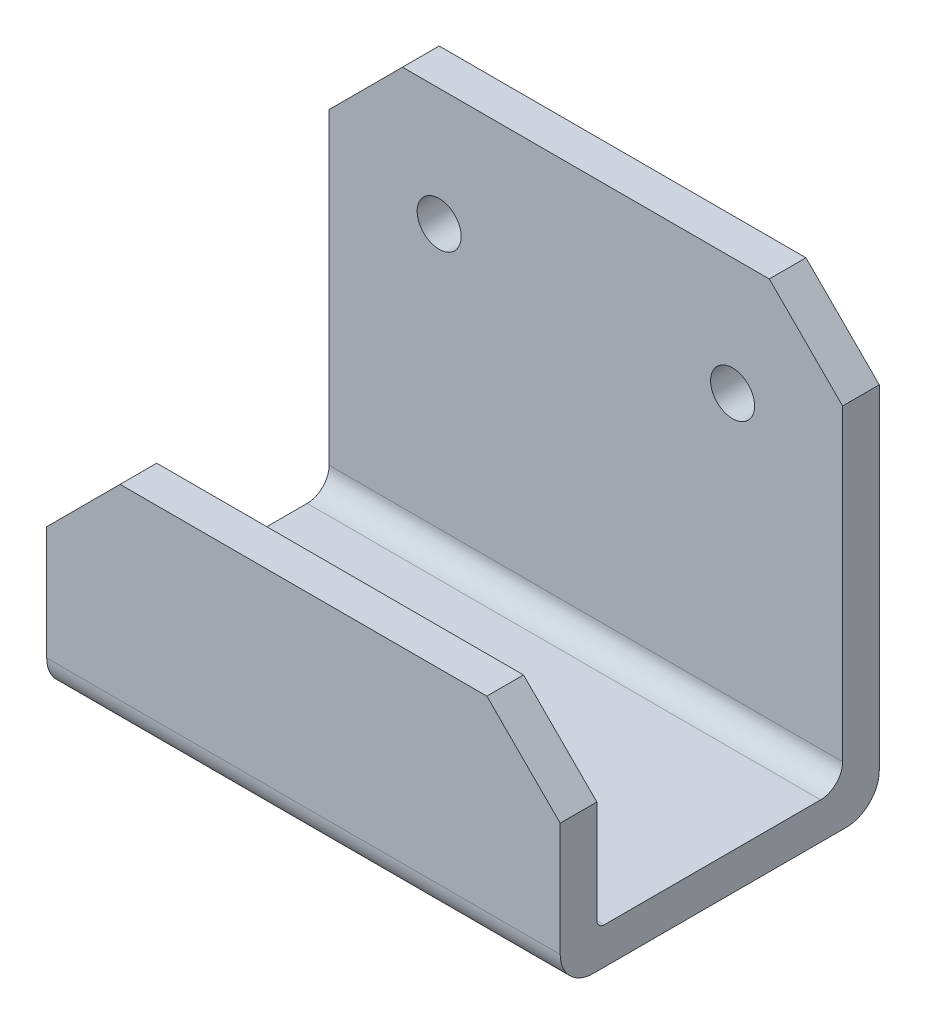
SolidWorks part; units mm, degrees
ref_plane "Front Plane" through (0, 0, 0) normal (0, 0, 1) x (1, 0, 0)
ref_plane "Top Plane" through (0, 0, 0) normal (0, 1, 0) x (1, 0, 0)
ref_plane "Right Plane" through (0, 0, 0) normal (1, 0, 0) x (0, 0, -1)
sketch "Sketch1" plane through (0, 0, 0) normal (1, 0, 0) x (0, 0, -1)
  line L0 (-21.75, 10) -> (-21.75, -20)
  line L1 (-21.75, -20) -> (21.75, -20)
  line L2 (21.75, -20) -> (21.75, 40)
  line L3 (21.75, 40) -> (16.75, 40)
  line L4 (16.75, 40) -> (16.75, -15)
  line L5 (16.75, -15) -> (-16.75, -15)
  line L6 (-16.75, -15) -> (-16.75, 10)
  line L7 (-16.75, 10) -> (-21.75, 10)
  dimension "D1" = 16.75
  dimension "D2" = 16.75
  dimension "D3" = 43.5
  dimension "D4" = 5
  dimension "D5" = 5
  dimension "D6" = 30
  dimension "D7" = 60
  dimension "D8" = 20
extrude "Boss-Extrude1" add sketch "Sketch1" along normal blind 35 and the other way blind 35
chamfer "Chamfer1" distance 10 angle 45 4 edges at (-35, 40, -19.25) (35, 40, -19.25) (35, 10, 19.25) (-35, 10, 19.25)
sketch "Sketch2" plane through (0, 0, -16.75) normal (0, 0, 1) x (1, 0, 0)
  line L0 (-35, 30) -> (-35, -15) construction
  line L1 (35, 30) -> (35, -15) construction
  circle A0 centre (-20, 24) radius 3
  circle A1 centre (20, 24) radius 3
  dimension "D3" = 6
  dimension "D4" = 6
  dimension "D1" = 15
  dimension "D2" = 15
  dimension "D5" = 6
  dimension "D6" = 6
extrude "Cut-Extrude1" cut sketch "Sketch2" against normal blind 35
fillet "Fillet1" radius 3 1 edges at (0, -15, -16.75)
fillet "Fillet2" radius 4.5 2 edges at (0, -20, 21.75) (0, -20, -21.75)
fillet "Fillet3" radius 1 1 edges at (0, -15, 16.75)
